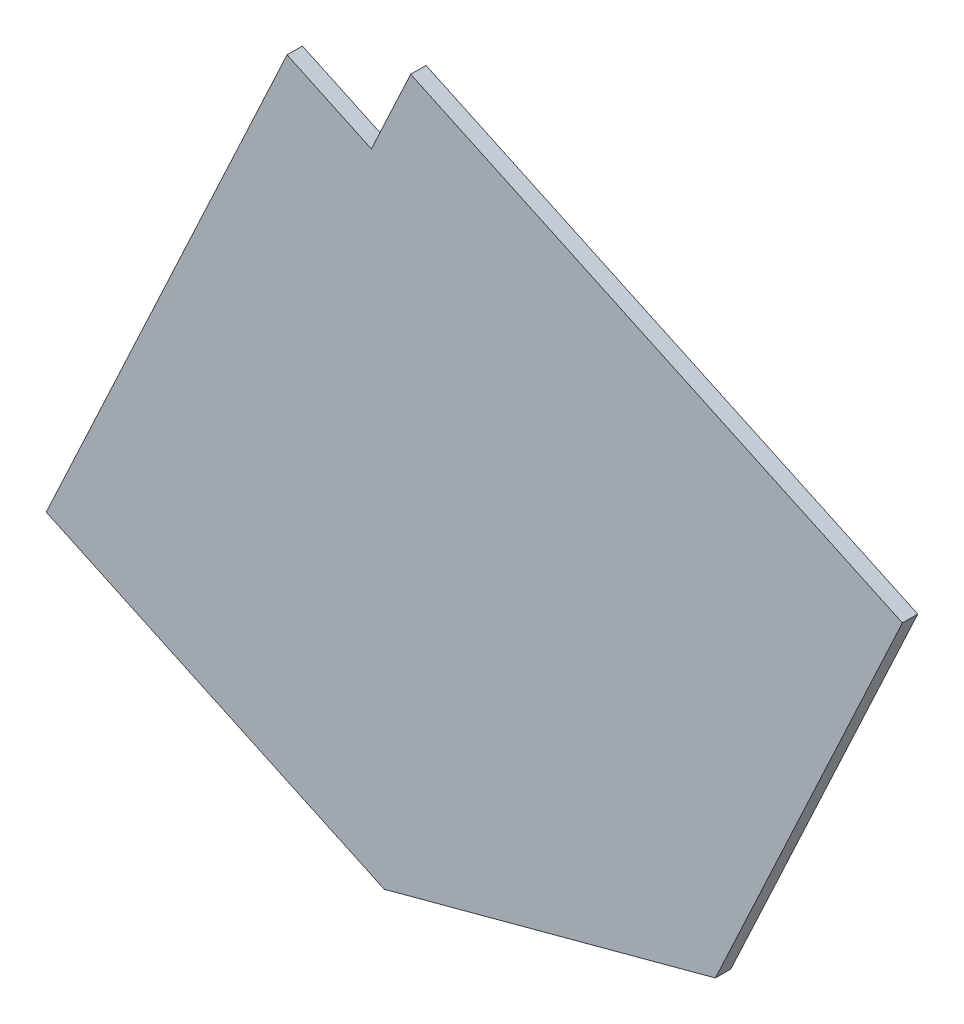
SolidWorks part; units mm, degrees
material "Balsa"
ref_plane "Front Plane" through (0, 0, 0) normal (0, 0, 1) x (1, 0, 0)
ref_plane "Top Plane" through (0, 0, 0) normal (0, 1, 0) x (1, 0, 0)
ref_plane "Right Plane" through (0, 0, 0) normal (1, 0, 0) x (0, 0, -1)
sketch "Sketch1" plane through (0, 0, 396.7) normal (0, 0, 1) x (1, 0, 0)
  line L0 (-365.9798, -82.6535) -> (-193.6829, -36.4866)
  line L2 (-365.9798, -82.6535) -> (-285.7774, 89.341)
  line L3 (-285.7774, 89.341) -> (-267.6513, 80.8887)
  line L4 (-267.6513, 80.8887) -> (-259.1989, 99.0148)
  line L5 (-259.1989, 99.0148) -> (-153.4844, 49.7193)
  line L6 (-153.4844, 49.7193) -> (-193.6829, -36.4866)
  line L8 (-255.5737, 97.3243) -> (63.4467, -51.4373) construction
  line L10 (-327.4362, 0.0035) -> (-285.7774, 89.341) construction
  line L11 (-285.7774, 89.341) -> (-267.6513, 80.8887) construction
  line L12 (-267.6513, 80.8887) -> (-259.1989, 99.0148) construction
  line L14 (-337.5482, -21.6817) -> (-264.8848, -55.5651)
  line L15 (-337.5482, -21.6817) -> (-334.5574, -23.0763) construction
  line L16 (-264.8848, -55.5651) -> (-193.6829, -36.4866) construction
  line L17 (-193.6829, -36.4866) -> (-153.4844, 49.7193) construction
  line M12 (-176.6689, 0) -> (-327.4378, 0)
  line M13 (-327.4378, 0) -> (-398.701, -152.8244)
  line M19 (-153.4844, 49.7193) -> (-176.6689, 0)
extrude "Boss-Extrude1" add sketch "Sketch1" against normal blind 3.3 contours L14 L0 L6 M13 M12 | L5 L4 L3 L2 M12 M19 region at (-256.45, -21.8244, 396.7) region at (-241.0759, 39.209, 396.7)
